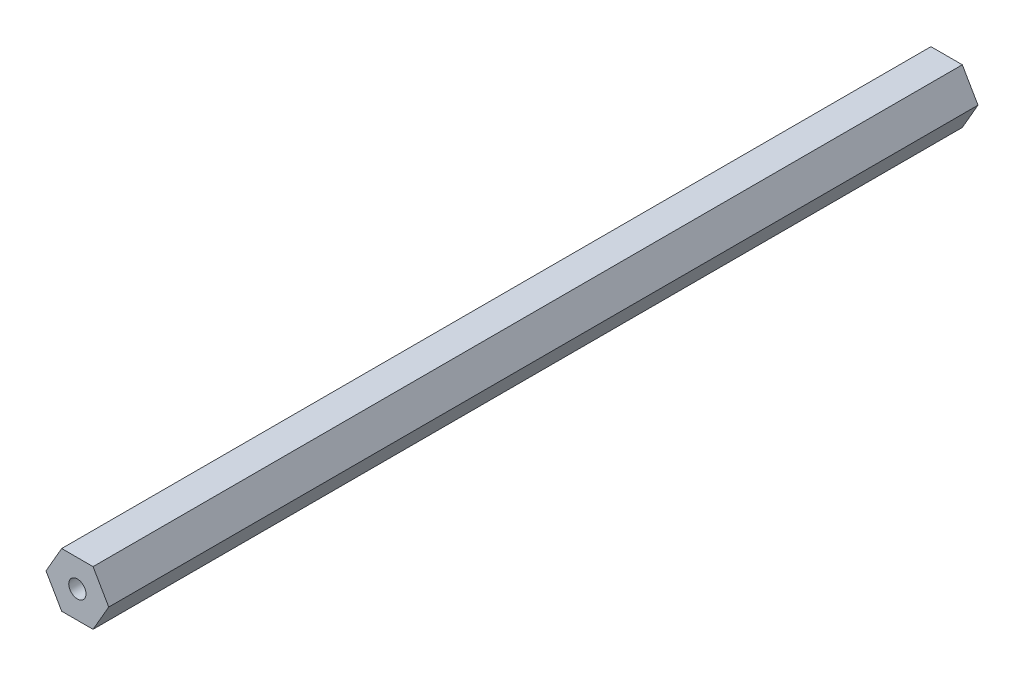
SolidWorks part; units mm, degrees
ref_plane "Front" through (0, 0, 0) normal (0, 0, 1) x (1, 0, 0)
ref_plane "Top" through (0, 0, 0) normal (0, 1, 0) x (1, 0, 0)
ref_plane "Right" through (0, 0, 0) normal (1, 0, 0) x (0, 0, -1)
sketch "Sketch1" plane through (0, 0, 0) normal (0, 0, 1) x (1, 0, 0)
  line L1 (7.3323, 0) -> (3.6662, 6.35)
  line L2 (3.6662, 6.35) -> (-3.6662, 6.35)
  line L3 (-3.6662, 6.35) -> (-7.3323, 0)
  line L4 (-7.3323, 0) -> (-3.6662, -6.35)
  line L5 (-3.6662, -6.35) -> (3.6662, -6.35)
  line L6 (3.6662, -6.35) -> (7.3323, 0)
  circle A0 centre (0, 0) radius 6.35 construction
  dimension "D1" = 12.7
extrude "Boss-Extrude1" add sketch "Sketch1" along normal blind 203.2
hole_wizard "#10-32 Tapped Hole1" positions "Sketch2" profile "Sketch4" tap size "#10-32" standard "ANSI Inch"
sketch "Sketch2" plane through (0, 0, 203.2) normal (0, 0, 1) x (1, 0, 0)
  point P0 (0, 0)
sketch "Sketch4" plane through (0, 0, 203.2) normal (1, 0, 0) x (0, -1, 0)
  line L0 (0, 0) -> (0, 77.4133)
  line L1 (0, 77.4133) -> (2.0193, 76.2)
  line L2 (2.0193, 76.2) -> (2.0193, 0)
  line L5 (2.0193, 0) -> (0, 0)
  line L10 (0, 77.4133) -> (-2.0193, 76.2) construction
  line L11 (0, -6.35) -> (0, 107.95) construction
  dimension "Tap Drill Dia." = 4.0386
  dimension "Tap Drill Depth" = 76.2
  dimension "Drill Angle" = 118
cosmetic thread "Hole Thread1" parameters "D1"=9.652, "D2"=4.826
